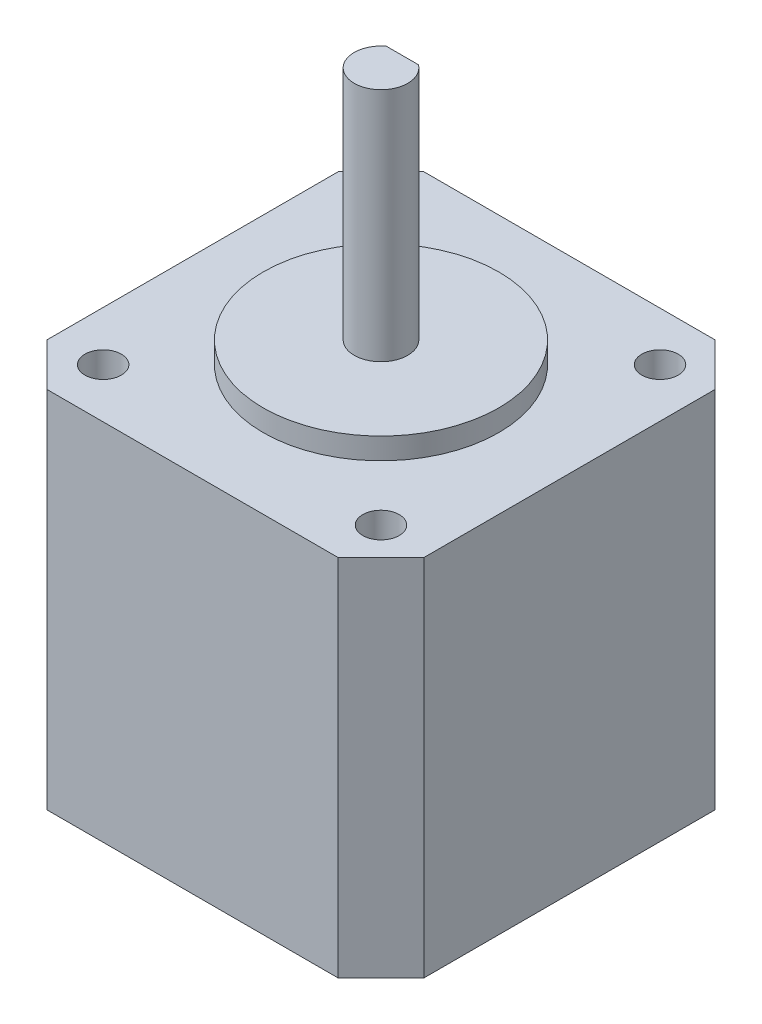
SolidWorks part; units mm, degrees
ref_plane "Front Plane" through (0, 0, 0) normal (0, 0, 1) x (1, 0, 0)
ref_plane "Top Plane" through (0, 0, 0) normal (0, 1, 0) x (1, 0, 0)
ref_plane "Right Plane" through (0, 0, 0) normal (1, 0, 0) x (0, 0, -1)
sketch "Sketch1" plane through (0, 0, 0) normal (0, 1, 0) x (1, 0, 0)
  line L0 (-15.3719, 11.5709) -> (-19.3719, 7.5709)
  line L1 (-15.3719, 11.5709) -> (11.8281, 11.5709)
  line L2 (-19.3719, 7.5709) -> (-19.3719, -19.6291)
  line L3 (-15.3719, -23.6291) -> (11.8281, -23.6291)
  line L4 (15.8281, 7.5709) -> (15.8281, -19.6291)
  line L5 (11.8281, 11.5709) -> (15.8281, 7.5709)
  line L6 (15.8281, -19.6291) -> (11.8281, -23.6291)
  line L7 (-19.3719, -19.6291) -> (-15.3719, -23.6291)
  line L8 (-19.3719, 11.5709) -> (15.8281, -23.6291)
  line L9 (-19.3719, -23.6291) -> (15.8281, 11.5709)
  circle A0 centre (-14.7444, 6.9434) radius 1.7
  circle A1 centre (11.2555, 6.9983) radius 1.7
  circle A2 centre (11.2007, -19.0017) radius 1.7
  circle A3 centre (-14.7445, -19.0017) radius 1.7
  point P0 (-19.3719, 11.5709)
  point P1 (15.8281, -23.6291)
  point P2 (-19.3719, -23.6291)
  point P3 (15.8281, 11.5709)
  point P20 (0, 0)
  point P21 (9.6719, 6.6264)
  point P24 (9.6719, -17.4729)
  point P25 (10.7925, 7.3517)
  point P28 (-15.1527, -18.5935)
  point P29 (11.2007, 6.9707)
  point P30 (-14.7444, -19.0017)
  dimension "D3" = 3.4
  dimension "D1" = 35.2
  dimension "D2" = 35.2
  dimension "D4" = 26
  dimension "D5" = 26
extrude "Boss-Extrude1" add sketch "Sketch1" along normal blind 34 contours A3 L9 L7 L3 L6 L8 A2 | A3 L9 L8 A0 L0 L2 L7 | A2 L8 L6 L4 L5 L9 A1 | A1 L9 L5 L1 L0 L8 A0 region at (-1.7728, 0, -5.5069) region at (-13.3089, 0, 6.0291) region at (9.7642, 0, 6.03) region at (-1.7719, 0, 17.5661)
sketch "Sketch2" plane through (0, 34, 0) normal (0, 1, 0) x (1, 0, 0)
  circle A0 centre (-1.7719, -6.0291) radius 11
  dimension "D1" = 22
extrude "Boss-Extrude2" add sketch "Sketch2" along normal blind 2
sketch "Sketch3" plane through (0, 36, 0) normal (0, 1, 0) x (1, 0, 0)
  circle A0 centre (-1.7719, -6.0291) radius 2.5
  dimension "D1" = 5
extrude "Boss-Extrude3" add sketch "Sketch3" along normal blind 5.5
sketch "Sketch4" plane through (0, 41.5, 0) normal (0, 1, 0) x (1, 0, 0)
  line L0 (-3.2719, -4.0291) -> (-0.2719, -4.0291)
  circle A0 centre (-1.7719, -6.0291) radius 2.5 construction
  arc A2 (-3.2719, -4.0291) -> (-0.2719, -4.0291) centre (-1.7719, -6.0291) ccw
extrude "Boss-Extrude4" add sketch "Sketch4" along normal blind 16.5
equation "\"m3_clearance\"=3.4"
equation "\"D3@Sketch1\"=\"m3_clearance\""
